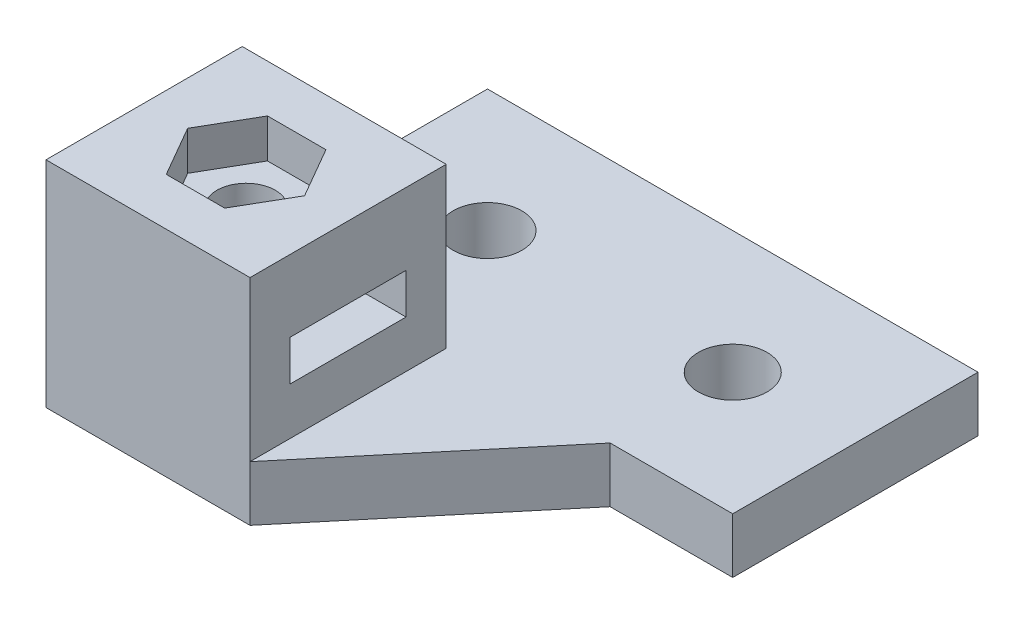
SolidWorks part; units mm, degrees
ref_plane "Front Plane" through (0, 0, 0) normal (0, 0, 1) x (1, 0, 0)
ref_plane "Top Plane" through (0, 0, 0) normal (0, 1, 0) x (1, 0, 0)
ref_plane "Right Plane" through (0, 0, 0) normal (1, 0, 0) x (0, 0, -1)
sketch "Sketch1" plane through (0, 0, 0) normal (0, 1, 0) x (1, 0, 0)
  line L0 (-10, 10) -> (30, 10)
  line L1 (30, 10) -> (30, -10)
  line L2 (30, -10) -> (6.6364, -10)
  line L3 (6.6364, -10) -> (6.6364, -26)
  line L4 (6.6364, -26) -> (-10, -26)
  line L7 (-10, -26) -> (-10, 10)
  line L8 (-26.7442, -18) -> (27.2503, -18) construction
  line L9 (30, 0) -> (-16.2534, 0) construction
  line L10 (6.6364, -26) -> (20, -10)
  line L11 (6.6364, -26) -> (-10, -26)
  line L12 (6.6364, -26) -> (6.6364, -10)
  line L13 (6.6364, -10) -> (-10, -10)
  line L14 (-10, -26) -> (-10, -10)
  circle A0 centre (0, 0) radius 2.8
  circle A1 centre (20, 0) radius 2.8
  point P13 (0, 0)
  point P21 (6.6364, -18)
  dimension "D2" = 5.6
  dimension "D1" = 20
  dimension "D3" = 18
  dimension "D4" = 10
  dimension "D5" = 10
  dimension "D6" = 10
extrude "Boss-Extrude1" add sketch "Sketch1" along normal blind 4.5 contours L13 L2 L1 L0 L7 A1 A0 | L3 L10 L2 region at (10, 0, 0) region at (11.0909, 0, 15.3333)
extrude "Boss-Extrude2" add sketch "Sketch1<3>" along normal blind 17.5 contours L3 L13 L7 L4 region at (-1.6818, 0, 18)
sketch "Sketch1<3>" plane through (0, 0, 0) normal (0, 1, 0) x (1, 0, 0) same geometry as "Sketch1"
ref_plane "Plane1" through (0, 0, 18) normal (0, 0, 1) x (1, 0, 0)
ref_plane "Plane2" through (0, 10, 0) normal (0, 1, 0) x (1, 0, 0)
sketch "Sketch2" plane through (6.6364, 0, 0) normal (1, 0, 0) x (0, 0, -1)
  line L0 (-18, 29.697) -> (-18, -29.697) construction
  line L1 (-22.725, 8.35) -> (-13.275, 8.35)
  line L2 (-22.725, 8.35) -> (-22.725, 11.65)
  line L3 (-22.725, 11.65) -> (-13.275, 11.65)
  line L4 (-13.275, 8.35) -> (-13.275, 11.65)
  line L5 (-22.725, 8.35) -> (-13.275, 11.65) construction
  line L6 (-22.725, 11.65) -> (-13.275, 8.35) construction
  line L7 (19.8, 10) -> (-19.8, 10) construction
  point P0 (-18, 10)
  point P5 (0, 0)
  dimension "D1" = 9.45
  dimension "D2" = 3.3
extrude "Cut-Extrude1" cut sketch "Sketch2" against normal through all contours L3 L4 L1 L2
ref_plane "Plane3" through (-1.6818, 0, 0) normal (1, 0, 0) x (0, 0, -1)
ref_axis "Axis1" through (-1.6818, 18.375, 18) along (0, -1, 0)
sketch "Sketch5" plane through (0, 17.5, 0) normal (0, 1, 0) x (1, 0, 0)
  line L0 (6.6364, -26) -> (-10, -26) construction
  line L1 (0.7012, -13.8725) -> (-4.0648, -13.8725)
  line L2 (-4.0648, -13.8725) -> (-6.4478, -18)
  line L3 (-6.4478, -18) -> (-4.0648, -22.1275)
  line L4 (-4.0648, -22.1275) -> (0.7012, -22.1275)
  line L5 (0.7012, -22.1275) -> (3.0842, -18)
  line L6 (3.0842, -18) -> (0.7012, -13.8725)
  circle A0 centre (-1.6818, -18) radius 4.1275 construction
  circle A1 centre (-1.6818, -18) radius 2.3813
  dimension "D2" = 4.7625
  dimension "D1" = 8.255
extrude "Cut-Extrude2" cut sketch "Sketch5" against normal blind 3.18 contours L4 L5 L6 L1 L2 L3
extrude "Cut-Extrude3" cut sketch "Sketch5<3>" against normal up to next contours A1
sketch "Sketch5<3>" plane through (0, 17.5, 0) normal (0, 1, 0) x (1, 0, 0) same geometry as "Sketch5"
equation "\"D6@Sketch1\"=\"D5@Sketch1\""
